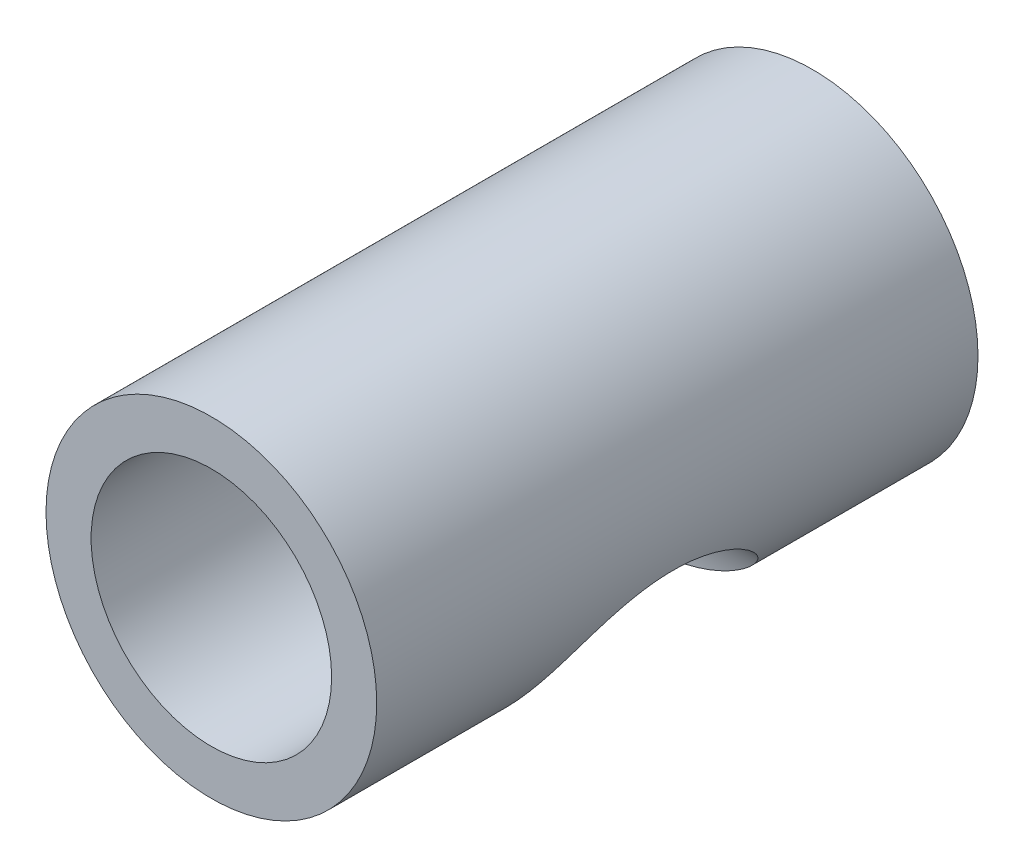
SolidWorks part; units mm, degrees
ref_plane "Front Plane" through (0, 0, 0) normal (0, 0, 1) x (1, 0, 0)
ref_plane "Top Plane" through (0, 0, 0) normal (0, 1, 0) x (1, 0, 0)
ref_plane "Right Plane" through (0, 0, 0) normal (1, 0, 0) x (0, 0, -1)
sketch "Sketch1" plane through (0, 0, 0) normal (0, 0, 1) x (1, 0, 0)
  circle A0 centre (0, 0) radius 16
  circle A1 centre (0, 0) radius 22
  dimension "D1" = 44
  dimension "D2" = 32
extrude "Boss-Extrude1" add sketch "Sketch1" along normal blind 40 and the other way blind 40
sketch "Sketch2" plane through (0, 0, 0) normal (1, 0, 0) x (0, 0, -1)
  circle A1 centre (0, -23) radius 18
  dimension "D1" = 36
  dimension "D2" = 23
extrude "Cut-Extrude1" cut sketch "Sketch2" against normal through all both and the other way through all
sketch "Sketch7" plane through (0, 0, 40) normal (0, 0, 1) x (1, 0, 0)
  circle A0 centre (0, 0) radius 16 construction
  circle A1 centre (0, 0) radius 16
curve "Helix/Spiral1" pitch 1.5 height 8 turns 5.3333
sketch "Sketch8" plane through (0, 0, 0) normal (0, 1, 0) x (1, 0, 0)
  line L0 (15.134, -39.5) -> (15.134, -40.5)
  line L3 (15.134, -40.5) -> (16, -40)
  line L4 (16, -40) -> (15.134, -39.5)
  line L5 (16, -40) -> (15.134, -40) construction
  point P2 (0, 0)
  dimension "D1" = 1
  dimension "D2" = 1
  dimension "D3" = 1
